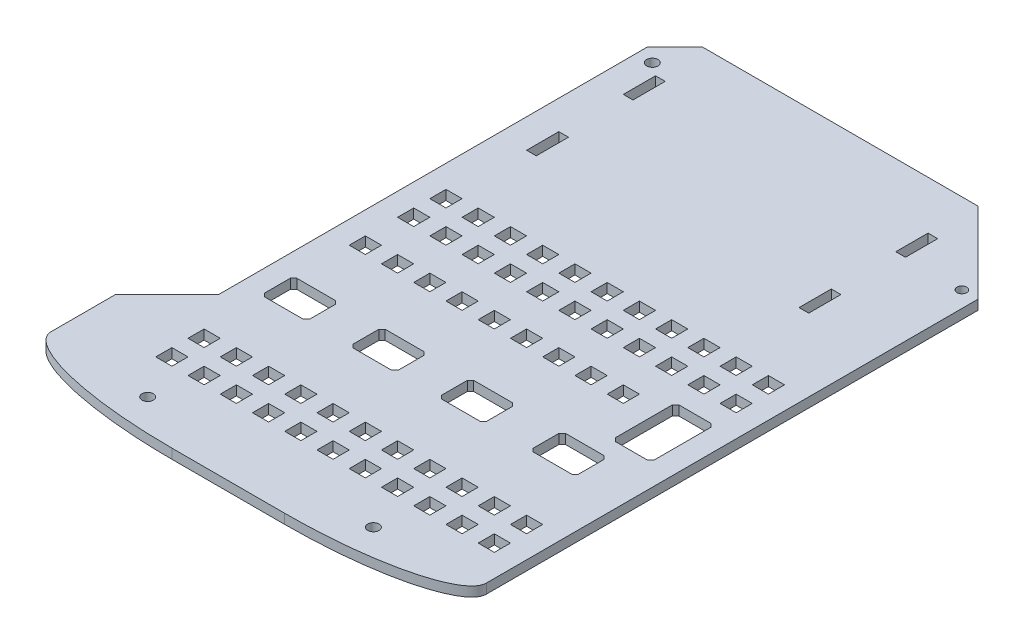
SolidWorks part; units mm, degrees
material "Balsa"
ref_plane "Alzado" through (0, 0, 0) normal (0, 0, 1) x (1, 0, 0)
ref_plane "Planta" through (0, 0, 0) normal (0, 1, 0) x (1, 0, 0)
ref_plane "Vista lateral" through (0, 0, 0) normal (1, 0, 0) x (0, 0, -1)
sketch "Sketch2" plane through (0, 0, 0) normal (0, 1, 0) x (1, 0, 0)
  line L1 (-67.5, 95) -> (67.5, 95)
  line L2 (-67.5, 95) -> (-67.5, -95)
  line L3 (-67.5, -95) -> (67.5, -95)
  line L4 (67.5, 95) -> (67.5, -95)
  line L5 (-67.5, 95) -> (67.5, -95) construction
  line L6 (-67.5, -95) -> (67.5, 95) construction
  point P0 (0, 0)
  dimension "D1" = 135
  dimension "D2" = 190
extrude "Boss-Extrude2" add sketch "Sketch2" along normal blind 3
fillet "Fillet1" radius 12.5 1 edges at (-67.5, 1.5, 95) second distance 50 first distance on face at (-67.5, 1.5, 0)
fillet "Fillet2" radius 12.5 1 edges at (67.5, 1.5, 95) second distance 50 first distance on face at (67.5, 1.5, 0)
sketch "Sketch6" plane through (0, 3, 0) normal (0, 1, 0) x (1, 0, 0)
  line L0 (0, -95) -> (0, 95) construction
  line L1 (-17.5, -95) -> (17.5, -95) construction
  line L2 (67.5, 95) -> (-67.5, 95) construction
  circle A0 centre (35, -85) radius 1.75
  circle A1 centre (-35, -85) radius 1.75
  dimension "D3" = 3.5
  dimension "D1" = 32.5
  dimension "D2" = 2.5
extrude "Cut-Extrude4" cut sketch "Sketch6" against normal blind 10
sketch "Sketch7" plane through (0, 3, 0) normal (0, 1, 0) x (1, 0, 0)
  line L2 (-51.5, 86.5147) -> (-51.5, -46.5)
  line L3 (-51.5, -46.5) -> (-67.5, -62.5)
  line L4 (-67.5, 95) -> (-67.5, -82.5) construction
  line L6 (-67.5, 95) -> (-67.5, -62.5)
  line L7 (-67.5, 95) -> (-43.0147, 95)
  line L8 (67.5, 95) -> (-67.5, 95) construction
  line L9 (-43.0147, 95) -> (-51.5, 86.5147)
  point P0 (0, 0)
  dimension "D1" = 16
  dimension "D2" = 45
  dimension "D3" = 20
  dimension "D4" = 45
  dimension "D5" = 12
extrude "Cut-Extrude5" cut sketch "Sketch7" against normal through all
sketch "Sketch8" plane through (0, 3, 0) normal (0, 1, 0) x (1, 0, 0)
  line L1 (-44.77, -30) -> (-30.77, -30)
  line L2 (-44.77, -30) -> (-44.77, -40)
  line L3 (-44.77, -40) -> (-30.77, -40)
  line L4 (-30.77, -30) -> (-30.77, -40)
  line L5 (-17.33, -30) -> (-3.33, -30)
  line L6 (-17.33, -30) -> (-17.33, -40)
  line L7 (-17.33, -40) -> (-3.33, -40)
  line L8 (-3.33, -30) -> (-3.33, -40)
  line L9 (10.11, -30) -> (24.11, -30)
  line L10 (10.11, -30) -> (10.11, -40)
  line L11 (10.11, -40) -> (24.11, -40)
  line L12 (24.11, -30) -> (24.11, -40)
  line L13 (38.55, -30) -> (52.55, -30)
  line L14 (38.55, -30) -> (38.55, -40)
  line L15 (38.55, -40) -> (52.55, -40)
  line L16 (52.55, -30) -> (52.55, -40)
  point P0 (-44.77, -30)
  point P3 (-30.77, -30)
  dimension "D1" = 55
  dimension "D2" = 27.27
  dimension "D3" = 14
  dimension "D4" = 10
  dimension "D5" = 13.44
  dimension "D6" = 13.44
  dimension "D7" = 14.44
extrude "Cut-Extrude6" cut sketch "Sketch8" against normal through all
chamfer "Chamfer1" distance 1 angle 45 4 edges at (-44.77, 1.5, 40) (-30.77, 1.5, 40) (-44.77, 1.5, 30) (-30.77, 1.5, 30)
chamfer "Chamfer2" distance 1 angle 45 12 edges at (-3.33, 1.5, 40) (-17.33, 1.5, 40) (10.11, 1.5, 40) (38.55, 1.5, 40) (52.55, 1.5, 40) (24.11, 1.5, 40) (-17.33, 1.5, 30) (10.11, 1.5, 30) (38.55, 1.5, 30) (52.55, 1.5, 30) (24.11, 1.5, 30) (-3.33, 1.5, 30)
sketch "Sketch9" plane through (0, 3, 0) normal (0, 1, 0) x (1, 0, 0)
  line L1 (48.48, -4.77) -> (60.48, -4.77)
  line L2 (48.48, -4.77) -> (48.48, -24.47)
  line L3 (48.48, -24.47) -> (60.48, -24.47)
  line L4 (60.48, -4.77) -> (60.48, -24.47)
  line L5 (48.48, -4.77) -> (60.48, -24.47) construction
  line L6 (48.48, -24.47) -> (60.48, -4.77) construction
  point P0 (54.48, -14.62)
  dimension "D1" = 70.53
  dimension "D2" = 30.98
  dimension "D3" = 12
  dimension "D4" = 19.7
extrude "Cut-Extrude7" cut sketch "Sketch9" against normal through all
chamfer "Chamfer3" distance 1 angle 45 4 edges at (48.48, 1.5, 24.47) (60.48, 1.5, 24.47) (60.48, 1.5, 4.77) (48.48, 1.5, 4.77)
chamfer "Chamfer4" distance 25 1 edges at (67.5, 1.5, -95)
sketch "Sketch11" plane through (0, 3, 0) normal (0, 1, 0) x (1, 0, 0)
  line L0 (45, 80) -> (45, 40) construction
  line L2 (42.5, 95) -> (-43.0147, 95) construction
  line L3 (-42.5, 80) -> (-42.5, 40) construction
  line L4 (-39.5, 50) -> (-42.5, 50)
  line L5 (-39.5, 50) -> (-39.5, 40)
  line L6 (-39.5, 40) -> (-42.5, 40)
  line L7 (-42.5, 50) -> (-42.5, 40)
  line L8 (-39.5, 80) -> (-42.5, 80)
  line L9 (-39.5, 80) -> (-39.5, 70)
  line L10 (-39.5, 70) -> (-42.5, 70)
  line L11 (-42.5, 80) -> (-42.5, 70)
  line L12 (-39.5, 40) -> (42, 40) construction
  line L13 (-17.5, -95) -> (17.5, -95) construction
  line L15 (45, 80) -> (42, 80)
  line L16 (45, 80) -> (45, 70)
  line L17 (45, 70) -> (42, 70)
  line L18 (42, 80) -> (42, 70)
  line L19 (45, 50) -> (42, 50)
  line L20 (45, 50) -> (45, 40)
  line L21 (45, 40) -> (42, 40)
  line L22 (42, 50) -> (42, 40)
  point P2 (0, -95)
  dimension "D1" = 3
  dimension "D2" = 10
  dimension "D3" = 20
  dimension "D4" = 15
  dimension "D5" = 81.5
  dimension "D6" = 42
extrude "Cut-Extrude9" cut sketch "Sketch11" against normal through all
sketch "Sketch12" plane through (0, 3, 0) normal (0, 1, 0) x (1, 0, 0)
  line L0 (-51.5, -46.5) -> (-51.5, 86.5147) construction
  line L1 (-44.5, 17) -> (-39.5, 17)
  line L2 (-44.5, 17) -> (-44.5, 12)
  line L3 (-44.5, 12) -> (-39.5, 12)
  line L4 (-39.5, 17) -> (-39.5, 12)
  line L221 (-34.5, 17) -> (-34.5, 12)
  line L222 (-34.5, 17) -> (-29.5, 17)
  line L223 (-29.5, 17) -> (-29.5, 12)
  line L224 (-34.5, 12) -> (-29.5, 12)
  line L225 (-24.5, 17) -> (-24.5, 12)
  line L226 (-24.5, 17) -> (-19.5, 17)
  line L227 (-19.5, 17) -> (-19.5, 12)
  line L228 (-24.5, 12) -> (-19.5, 12)
  line L229 (-14.5, 17) -> (-14.5, 12)
  line L230 (-14.5, 17) -> (-9.5, 17)
  line L231 (-9.5, 17) -> (-9.5, 12)
  line L232 (-14.5, 12) -> (-9.5, 12)
  line L233 (-4.5, 17) -> (-4.5, 12)
  line L234 (-4.5, 17) -> (0.5, 17)
  line L235 (0.5, 17) -> (0.5, 12)
  line L236 (-4.5, 12) -> (0.5, 12)
  line L237 (5.5, 17) -> (5.5, 12)
  line L238 (5.5, 17) -> (10.5, 17)
  line L239 (10.5, 17) -> (10.5, 12)
  line L240 (5.5, 12) -> (10.5, 12)
  line L241 (15.5, 17) -> (15.5, 12)
  line L242 (15.5, 17) -> (20.5, 17)
  line L243 (20.5, 17) -> (20.5, 12)
  line L244 (15.5, 12) -> (20.5, 12)
  line L245 (25.5, 17) -> (25.5, 12)
  line L246 (25.5, 17) -> (30.5, 17)
  line L247 (30.5, 17) -> (30.5, 12)
  line L248 (25.5, 12) -> (30.5, 12)
  line L249 (35.5, 17) -> (35.5, 12)
  line L250 (35.5, 17) -> (40.5, 17)
  line L251 (40.5, 17) -> (40.5, 12)
  line L252 (35.5, 12) -> (40.5, 12)
  line L253 (45.5, 17) -> (45.5, 12)
  line L254 (45.5, 17) -> (50.5, 17)
  line L255 (50.5, 17) -> (50.5, 12)
  line L256 (45.5, 12) -> (50.5, 12)
  line L257 (55.5, 17) -> (55.5, 12)
  line L258 (55.5, 17) -> (60.5, 17)
  line L259 (60.5, 17) -> (60.5, 12)
  line L260 (55.5, 12) -> (60.5, 12)
  line L261 (-34.5, -8) -> (-34.5, -13)
  line L262 (-34.5, -8) -> (-29.5, -8)
  line L263 (-29.5, -8) -> (-29.5, -13)
  line L264 (-34.5, -13) -> (-29.5, -13)
  line L265 (-24.5, -8) -> (-24.5, -13)
  line L266 (-24.5, -8) -> (-19.5, -8)
  line L267 (-19.5, -8) -> (-19.5, -13)
  line L268 (-24.5, -13) -> (-19.5, -13)
  line L269 (-14.5, -8) -> (-14.5, -13)
  line L270 (-14.5, -8) -> (-9.5, -8)
  line L271 (-9.5, -8) -> (-9.5, -13)
  line L272 (-14.5, -13) -> (-9.5, -13)
  line L273 (-4.5, -8) -> (-4.5, -13)
  line L274 (-4.5, -8) -> (0.5, -8)
  line L275 (0.5, -8) -> (0.5, -13)
  line L276 (-4.5, -13) -> (0.5, -13)
  line L277 (5.5, -8) -> (5.5, -13)
  line L278 (5.5, -8) -> (10.5, -8)
  line L279 (10.5, -8) -> (10.5, -13)
  line L280 (5.5, -13) -> (10.5, -13)
  line L281 (15.5, -8) -> (15.5, -13)
  line L282 (15.5, -8) -> (20.5, -8)
  line L283 (20.5, -8) -> (20.5, -13)
  line L284 (15.5, -13) -> (20.5, -13)
  line L285 (25.5, -8) -> (25.5, -13)
  line L286 (25.5, -8) -> (30.5, -8)
  line L287 (30.5, -8) -> (30.5, -13)
  line L288 (25.5, -13) -> (30.5, -13)
  line L289 (35.5, -8) -> (35.5, -13)
  line L290 (35.5, -8) -> (40.5, -8)
  line L291 (40.5, -8) -> (40.5, -13)
  line L292 (35.5, -13) -> (40.5, -13)
  line L341 (-34.5, -58) -> (-34.5, -63)
  line L342 (-34.5, -58) -> (-29.5, -58)
  line L343 (-29.5, -58) -> (-29.5, -63)
  line L344 (-34.5, -63) -> (-29.5, -63)
  line L345 (-24.5, -58) -> (-24.5, -63)
  line L346 (-24.5, -58) -> (-19.5, -58)
  line L347 (-19.5, -58) -> (-19.5, -63)
  line L348 (-24.5, -63) -> (-19.5, -63)
  line L349 (-14.5, -58) -> (-14.5, -63)
  line L350 (-14.5, -58) -> (-9.5, -58)
  line L351 (-9.5, -58) -> (-9.5, -63)
  line L352 (-14.5, -63) -> (-9.5, -63)
  line L353 (-4.5, -58) -> (-4.5, -63)
  line L354 (-4.5, -58) -> (0.5, -58)
  line L355 (0.5, -58) -> (0.5, -63)
  line L356 (-4.5, -63) -> (0.5, -63)
  line L357 (5.5, -58) -> (5.5, -63)
  line L358 (5.5, -58) -> (10.5, -58)
  line L359 (10.5, -58) -> (10.5, -63)
  line L360 (5.5, -63) -> (10.5, -63)
  line L361 (15.5, -58) -> (15.5, -63)
  line L362 (15.5, -58) -> (20.5, -58)
  line L363 (20.5, -58) -> (20.5, -63)
  line L364 (15.5, -63) -> (20.5, -63)
  line L365 (25.5, -58) -> (25.5, -63)
  line L366 (25.5, -58) -> (30.5, -58)
  line L367 (30.5, -58) -> (30.5, -63)
  line L368 (25.5, -63) -> (30.5, -63)
  line L369 (35.5, -58) -> (35.5, -63)
  line L370 (35.5, -58) -> (40.5, -58)
  line L371 (40.5, -58) -> (40.5, -63)
  line L372 (35.5, -63) -> (40.5, -63)
  line L373 (45.5, -58) -> (45.5, -63)
  line L374 (45.5, -58) -> (50.5, -58)
  line L375 (50.5, -58) -> (50.5, -63)
  line L376 (45.5, -63) -> (50.5, -63)
  line L377 (55.5, -58) -> (55.5, -63)
  line L378 (55.5, -58) -> (60.5, -58)
  line L379 (60.5, -58) -> (60.5, -63)
  line L380 (55.5, -63) -> (60.5, -63)
  line L381 (-44.5, -8) -> (-44.5, -13)
  line L382 (-44.5, -8) -> (-39.5, -8)
  line L383 (-39.5, -8) -> (-39.5, -13)
  line L384 (-44.5, -13) -> (-39.5, -13)
  line L389 (-44.5, -58) -> (-44.5, -63)
  line L390 (-44.5, -58) -> (-39.5, -58)
  line L391 (-39.5, -58) -> (-39.5, -63)
  line L392 (-44.5, -63) -> (-39.5, -63)
  line L393 (42.5, 95) -> (-43.0147, 95) construction
  line L437 (-34.5, -33) -> (-34.5, -38) [skipped]
  line L438 (-34.5, -33) -> (-29.5, -33) [skipped]
  line L439 (-29.5, -33) -> (-29.5, -38) [skipped]
  line L440 (-34.5, -38) -> (-29.5, -38) [skipped]
  line L441 (-24.5, -33) -> (-24.5, -38) [skipped]
  line L442 (-24.5, -33) -> (-19.5, -33) [skipped]
  line L443 (-19.5, -33) -> (-19.5, -38) [skipped]
  line L444 (-24.5, -38) -> (-19.5, -38) [skipped]
  line L445 (-14.5, -33) -> (-14.5, -38) [skipped]
  line L446 (-14.5, -33) -> (-9.5, -33) [skipped]
  line L447 (-9.5, -33) -> (-9.5, -38) [skipped]
  line L448 (-14.5, -38) -> (-9.5, -38) [skipped]
  line L449 (-4.5, -33) -> (-4.5, -38) [skipped]
  line L450 (-4.5, -33) -> (0.5, -33) [skipped]
  line L451 (0.5, -33) -> (0.5, -38) [skipped]
  line L452 (-4.5, -38) -> (0.5, -38) [skipped]
  line L453 (5.5, -33) -> (5.5, -38) [skipped]
  line L454 (5.5, -33) -> (10.5, -33) [skipped]
  line L455 (10.5, -33) -> (10.5, -38) [skipped]
  line L456 (5.5, -38) -> (10.5, -38) [skipped]
  line L457 (15.5, -33) -> (15.5, -38) [skipped]
  line L458 (15.5, -33) -> (20.5, -33) [skipped]
  line L459 (20.5, -33) -> (20.5, -38) [skipped]
  line L460 (15.5, -38) -> (20.5, -38) [skipped]
  line L461 (25.5, -33) -> (25.5, -38) [skipped]
  line L462 (25.5, -33) -> (30.5, -33) [skipped]
  line L463 (30.5, -33) -> (30.5, -38) [skipped]
  line L464 (25.5, -38) -> (30.5, -38) [skipped]
  line L465 (35.5, -33) -> (35.5, -38) [skipped]
  line L466 (35.5, -33) -> (40.5, -33) [skipped]
  line L467 (40.5, -33) -> (40.5, -38) [skipped]
  line L468 (35.5, -38) -> (40.5, -38) [skipped]
  line L469 (45.5, -33) -> (45.5, -38) [skipped]
  line L470 (45.5, -33) -> (50.5, -33) [skipped]
  line L471 (50.5, -33) -> (50.5, -38) [skipped]
  line L472 (45.5, -38) -> (50.5, -38) [skipped]
  line L473 (55.5, -33) -> (55.5, -38) [skipped]
  line L474 (55.5, -33) -> (60.5, -33) [skipped]
  line L475 (60.5, -33) -> (60.5, -38) [skipped]
  line L476 (55.5, -38) -> (60.5, -38) [skipped]
  line L477 (-44.5, -33) -> (-44.5, -38) [skipped]
  line L478 (-44.5, -33) -> (-39.5, -33) [skipped]
  line L479 (-39.5, -33) -> (-39.5, -38) [skipped]
  line L480 (-44.5, -38) -> (-39.5, -38) [skipped]
  line L481 (45.5, -8) -> (45.5, -13) [skipped]
  line L482 (45.5, -8) -> (50.5, -8) [skipped]
  line L483 (50.5, -8) -> (50.5, -13) [skipped]
  line L484 (45.5, -13) -> (50.5, -13) [skipped]
  line L485 (55.5, -8) -> (55.5, -13) [skipped]
  line L486 (55.5, -8) -> (60.5, -8) [skipped]
  line L487 (60.5, -8) -> (60.5, -13) [skipped]
  line L488 (55.5, -13) -> (60.5, -13) [skipped]
  dimension "D1" = 5
  dimension "D2" = 7
  dimension "D3" = 78
  dimension "D4" = 11
  dimension "D5" = 4
extrude "Cut-Extrude10" cut sketch "Sketch12" against normal through all
sketch "Sketch13" plane through (0, 3, 0) normal (0, 1, 0) x (1, 0, 0)
  line L0 (-44.5, 17) -> (-44.5, 12) construction
  line L1 (-44.5, -68) -> (-39.5, -68)
  line L2 (-44.5, -68) -> (-44.5, -73)
  line L3 (-44.5, -73) -> (-39.5, -73)
  line L4 (-39.5, -68) -> (-39.5, -73)
  line L5 (-44.5, -58) -> (-44.5, -63) construction
  line L6 (-34.5, -68) -> (-34.5, -73)
  line L7 (-34.5, -68) -> (-29.5, -68)
  line L8 (-29.5, -68) -> (-29.5, -73)
  line L9 (-34.5, -73) -> (-29.5, -73)
  line L10 (-24.5, -68) -> (-24.5, -73)
  line L11 (-24.5, -68) -> (-19.5, -68)
  line L12 (-19.5, -68) -> (-19.5, -73)
  line L13 (-24.5, -73) -> (-19.5, -73)
  line L14 (-14.5, -68) -> (-14.5, -73)
  line L15 (-14.5, -68) -> (-9.5, -68)
  line L16 (-9.5, -68) -> (-9.5, -73)
  line L17 (-14.5, -73) -> (-9.5, -73)
  line L18 (-4.5, -68) -> (-4.5, -73)
  line L19 (-4.5, -68) -> (0.5, -68)
  line L20 (0.5, -68) -> (0.5, -73)
  line L21 (-4.5, -73) -> (0.5, -73)
  line L22 (5.5, -68) -> (5.5, -73)
  line L23 (5.5, -68) -> (10.5, -68)
  line L24 (10.5, -68) -> (10.5, -73)
  line L25 (5.5, -73) -> (10.5, -73)
  line L26 (15.5, -68) -> (15.5, -73)
  line L27 (15.5, -68) -> (20.5, -68)
  line L28 (20.5, -68) -> (20.5, -73)
  line L29 (15.5, -73) -> (20.5, -73)
  line L30 (25.5, -68) -> (25.5, -73)
  line L31 (25.5, -68) -> (30.5, -68)
  line L32 (30.5, -68) -> (30.5, -73)
  line L33 (25.5, -73) -> (30.5, -73)
  line L34 (35.5, -68) -> (35.5, -73)
  line L35 (35.5, -68) -> (40.5, -68)
  line L36 (40.5, -68) -> (40.5, -73)
  line L37 (35.5, -73) -> (40.5, -73)
  line L38 (45.5, -68) -> (45.5, -73)
  line L39 (45.5, -68) -> (50.5, -68)
  line L40 (50.5, -68) -> (50.5, -73)
  line L41 (45.5, -73) -> (50.5, -73)
  line L42 (55.5, -68) -> (55.5, -73)
  line L43 (55.5, -68) -> (60.5, -68)
  line L44 (60.5, -68) -> (60.5, -73)
  line L45 (55.5, -73) -> (60.5, -73)
  line L46 (-34.5, 7) -> (-34.5, 2)
  line L47 (-44.5, 7) -> (-39.5, 7)
  line L48 (-44.5, 7) -> (-44.5, 2)
  line L49 (-44.5, 2) -> (-39.5, 2)
  line L50 (-39.5, 7) -> (-39.5, 2)
  line L51 (-34.5, 7) -> (-29.5, 7)
  line L52 (-29.5, 7) -> (-29.5, 2)
  line L53 (-34.5, 2) -> (-29.5, 2)
  line L54 (-24.5, 7) -> (-24.5, 2)
  line L55 (-24.5, 7) -> (-19.5, 7)
  line L56 (-19.5, 7) -> (-19.5, 2)
  line L57 (-24.5, 2) -> (-19.5, 2)
  line L58 (-14.5, 7) -> (-14.5, 2)
  line L59 (-14.5, 7) -> (-9.5, 7)
  line L60 (-9.5, 7) -> (-9.5, 2)
  line L61 (-14.5, 2) -> (-9.5, 2)
  line L62 (-4.5, 7) -> (-4.5, 2)
  line L63 (-4.5, 7) -> (0.5, 7)
  line L64 (0.5, 7) -> (0.5, 2)
  line L65 (-4.5, 2) -> (0.5, 2)
  line L66 (5.5, 7) -> (5.5, 2)
  line L67 (5.5, 7) -> (10.5, 7)
  line L68 (10.5, 7) -> (10.5, 2)
  line L69 (5.5, 2) -> (10.5, 2)
  line L70 (15.5, 7) -> (15.5, 2)
  line L71 (15.5, 7) -> (20.5, 7)
  line L72 (20.5, 7) -> (20.5, 2)
  line L73 (15.5, 2) -> (20.5, 2)
  line L74 (25.5, 7) -> (25.5, 2)
  line L75 (25.5, 7) -> (30.5, 7)
  line L76 (30.5, 7) -> (30.5, 2)
  line L77 (25.5, 2) -> (30.5, 2)
  line L78 (35.5, 7) -> (35.5, 2)
  line L79 (35.5, 7) -> (40.5, 7)
  line L80 (40.5, 7) -> (40.5, 2)
  line L81 (35.5, 2) -> (40.5, 2)
  line L82 (45.5, 7) -> (45.5, 2)
  line L83 (45.5, 7) -> (50.5, 7)
  line L84 (50.5, 7) -> (50.5, 2)
  line L85 (45.5, 2) -> (50.5, 2)
  line L86 (55.5, 7) -> (55.5, 2)
  line L87 (55.5, 7) -> (60.5, 7)
  line L88 (60.5, 7) -> (60.5, 2)
  line L89 (55.5, 2) -> (60.5, 2)
  point P6 (-44.5, 14.5)
  point P7 (-44.5, -70.5)
  point P54 (-44.5, 4.5)
  dimension "D1" = 85
  dimension "D2" = 5
  dimension "D4" = 5
  dimension "D5" = 10
  dimension "D3" = 11
  dimension "D6" = 11
extrude "Cut-Extrude11" cut sketch "Sketch13" against normal through all
sketch "Sketch14" plane through (0, 3, 0) normal (0, 1, 0) x (1, 0, 0)
  line L0 (67.5, -82.5) -> (67.5, 70) construction
  line L2 (42.5, 95) -> (-43.0147, 95) construction
  circle A0 centre (62.5, 70) radius 1.5
  circle A2 centre (-46.5147, 83) radius 1.75
  dimension "D1" = 3
  dimension "D5" = 3.5
  dimension "D2" = 5
  dimension "D3" = 12
  dimension "D4" = 3.5
  dimension "D6" = 25
extrude "Cut-Extrude12" cut sketch "Sketch14" against normal blind 10
